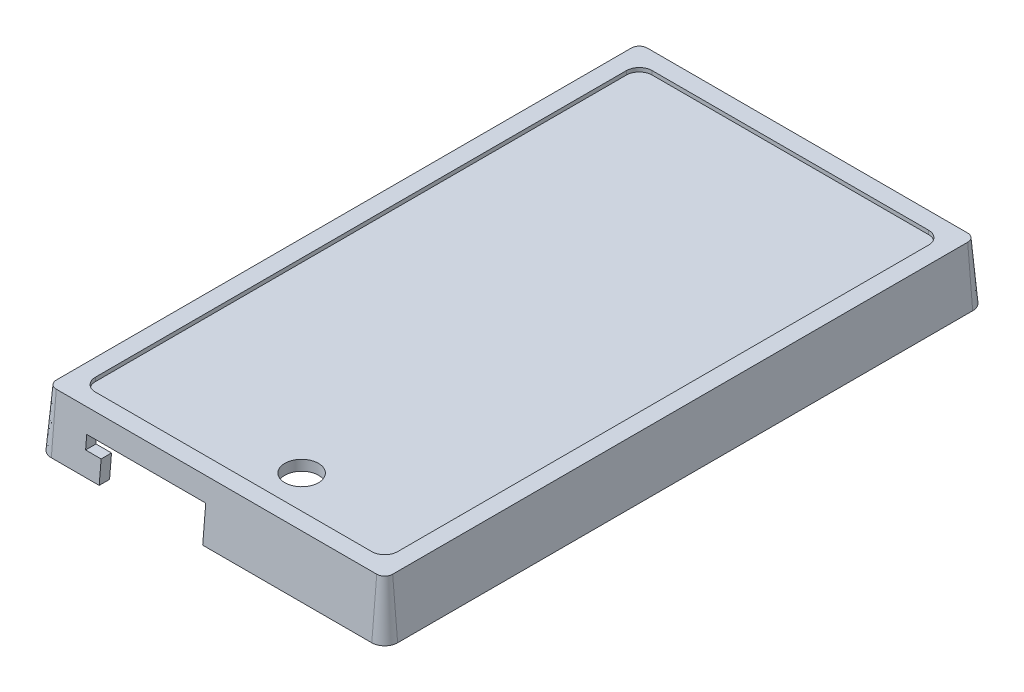
SolidWorks part; units mm, degrees
ref_plane "Спереди" through (0, 0, 0) normal (0, 0, 1) x (1, 0, 0)
ref_plane "Сверху" through (0, 0, 0) normal (0, 1, 0) x (1, 0, 0)
ref_plane "Справа" through (0, 0, 0) normal (1, 0, 0) x (0, 0, -1)
sketch "Sketch1" plane through (0, 0, 0) normal (0, 1, 0) x (1, 0, 0)
  line L1 (-1, 0) -> (-25.77, 0)
  line L2 (0, 1) -> (0, 45.45)
  line L3 (-1, 46.45) -> (-25.77, 46.45)
  line L4 (-26.77, 1) -> (-26.77, 45.45)
  arc A0 (0, 45.45) -> (-1, 46.45) centre (-1, 45.45) ccw
  arc A1 (-1, 0) -> (0, 1) centre (-1, 1) ccw
  arc A2 (-26.77, 1) -> (-25.77, 0) centre (-25.77, 1) ccw
  arc A3 (-26.77, 45.45) -> (-25.77, 46.45) centre (-25.77, 45.45) cw
  point P7 (0, 46.45)
  point P10 (0, 0)
  point P15 (-26.77, 46.45)
  dimension "D3" = 1
  dimension "D1" = 26.77
  dimension "D2" = 46.45
extrude "Boss-Extrude1" add sketch "Sketch1" along normal blind 4.4 draft 5
sketch "Sketch2" plane through (0, 4.4, 0) normal (0, 1, 0) x (1, 0, 0)
  line L0 (-26.385, 45.45) -> (-26.385, 1) construction
  line L1 (-24.065, 44.745) -> (-2.705, 44.745)
  line L2 (-25.065, 43.745) -> (-25.065, 2.705)
  line L3 (-24.065, 1.705) -> (-2.705, 1.705)
  line L4 (-1.705, 43.745) -> (-1.705, 2.705)
  line L5 (-1, 46.065) -> (-25.77, 46.065) construction
  line L6 (-0.385, 1) -> (-0.385, 45.45) construction
  line L7 (-25.77, 0.385) -> (-1, 0.385) construction
  arc A0 (-1.705, 43.745) -> (-2.705, 44.745) centre (-2.705, 43.745) ccw
  arc A1 (-1.705, 2.705) -> (-2.705, 1.705) centre (-2.705, 2.705) cw
  arc A2 (-25.065, 2.705) -> (-24.065, 1.705) centre (-24.065, 2.705) ccw
  arc A3 (-25.065, 43.745) -> (-24.065, 44.745) centre (-24.065, 43.745) cw
  dimension "D5" = 1
  dimension "D1" = 1.32
  dimension "D2" = 1.32
  dimension "D3" = 1.32
  dimension "D4" = 1.32
extrude "Cut-Extrude1" cut sketch "Sketch2" against normal blind 0.3
shell "Shell1" thickness 0.8 removed face at (-13.385, 0, -23.225)
sketch "Sketch3" plane through (0, 4.1, 0) normal (0, 1, 0) x (1, 0, 0)
  line L0 (-25.77, 0.385) -> (-1, 0.385) construction
  line L1 (-0.385, 1) -> (-0.385, 45.45) construction
  circle A0 centre (-10.975, 4.555) radius 1.3
  dimension "D1" = 2.6
  dimension "D2" = 2.87
  dimension "D3" = 9.29
extrude "Cut-Extrude2" cut sketch "Sketch3" against normal through all
sketch "Sketch4" plane through (0, 0, 0) normal (0, 0, 1) x (1, 0, 0)
  line L0 (-22.07, 0) -> (-22.07, 1.7)
  line L1 (-25.77, 0) -> (-1, 0) construction
  line L2 (-22.07, 1.7) -> (-23.27, 1.7)
  line L3 (-23.27, 1.7) -> (-23.27, 2.7)
  line L4 (-23.27, 2.7) -> (-14.07, 2.7)
  line L5 (-14.07, 2.7) -> (-14.07, 0)
  line L6 (-14.07, 0) -> (-22.07, 0)
  line L7 (-25.77, 4.4) -> (-25.77, 0) construction
  dimension "D1" = 2.7
  dimension "D2" = 9.2
  dimension "D3" = 2.5
  dimension "D4" = 8
  dimension "D5" = 1
extrude "Cut-Extrude3" cut sketch "Sketch4" against normal up to surface (0.8031 mm away) up to face at (-13.385, 2.5498, -1.0261)
sketch "Sketch6" plane through (0, 0, 0) normal (0, 0, 1) x (1, 0, 0)
  line L0 (-24.11, 0) -> (-24.11, 3)
  line L1 (-25.77, 0) -> (-22.07, 0) construction
  line L2 (-24.11, 3) -> (-2.66, 3)
  line L3 (-2.66, 3) -> (-2.66, 0)
  line L4 (-14.07, 0) -> (-1, 0) construction
  line L5 (-2.66, 0) -> (-24.11, 0)
  line L6 (-13.385, 3.3) -> (-13.385, -2.6343) construction
  line L7 (-1.9064, 3.3) -> (-24.8636, 3.3) construction
  dimension "D1" = 21.45
  dimension "D2" = 10.725
  dimension "D3" = 3
extrude "Cut-Extrude4" cut sketch "Sketch6" against normal up to surface (1.0918 mm away) from vertex up to face at (-13.385, 2.2, -46.2575) starting at point (-1.9064, 3.3, -45.3582)
sketch "Sketch7" plane through (0, 0, 0) normal (0, 0, 1) x (1, 0, 0)
  line L0 (-8.81, 3) -> (-7.51, 3)
  line L1 (-6.26, 3) -> (-4.96, 3)
  line L2 (-6.26, 3) -> (-6.26, 3.6)
  line L3 (-6.26, 3.6) -> (-4.96, 3.6)
  line L4 (-4.96, 3) -> (-4.96, 3.6)
  line L5 (-8.81, 3) -> (-8.81, 3.6)
  line L6 (-8.81, 3.6) -> (-7.51, 3.6)
  line L7 (-24.11, 3) -> (-2.66, 3) construction
  line L8 (-2.66, 3) -> (-2.66, 0) construction
  line L9 (-7.51, 3) -> (-7.51, 3.6)
  line L10 (-11.36, 3) -> (-10.06, 3)
  line L11 (-11.36, 3) -> (-11.36, 3.6)
  line L12 (-11.36, 3.6) -> (-10.06, 3.6)
  line L13 (-10.06, 3) -> (-10.06, 3.6)
  line L14 (-13.91, 3) -> (-12.61, 3)
  line L15 (-13.91, 3) -> (-13.91, 3.6)
  line L16 (-13.91, 3.6) -> (-12.61, 3.6)
  line L17 (-12.61, 3) -> (-12.61, 3.6)
  line L18 (-16.46, 3) -> (-15.16, 3)
  line L19 (-16.46, 3) -> (-16.46, 3.6)
  line L20 (-16.46, 3.6) -> (-15.16, 3.6)
  line L21 (-15.16, 3) -> (-15.16, 3.6)
  line L22 (-19.01, 3) -> (-17.71, 3)
  line L23 (-19.01, 3) -> (-19.01, 3.6)
  line L24 (-19.01, 3.6) -> (-17.71, 3.6)
  line L25 (-17.71, 3) -> (-17.71, 3.6)
  line L26 (-21.56, 3) -> (-20.26, 3)
  line L27 (-21.56, 3) -> (-21.56, 3.6)
  line L28 (-21.56, 3.6) -> (-20.26, 3.6)
  line L29 (-20.26, 3) -> (-20.26, 3.6)
  line L30 (-24.11, 3) -> (-22.81, 3)
  line L31 (-24.11, 3) -> (-24.11, 3.6)
  line L32 (-24.11, 3.6) -> (-22.81, 3.6)
  line L33 (-22.81, 3) -> (-22.81, 3.6)
  dimension "D1" = 1.3
  dimension "D2" = 0.6
  dimension "D3" = 2.3
  dimension "D4" = 8
extrude "Cut-Extrude5" cut sketch "Sketch7" along normal blind 8.5 from vertex starting at point (-24.11, 0, -46.45)
